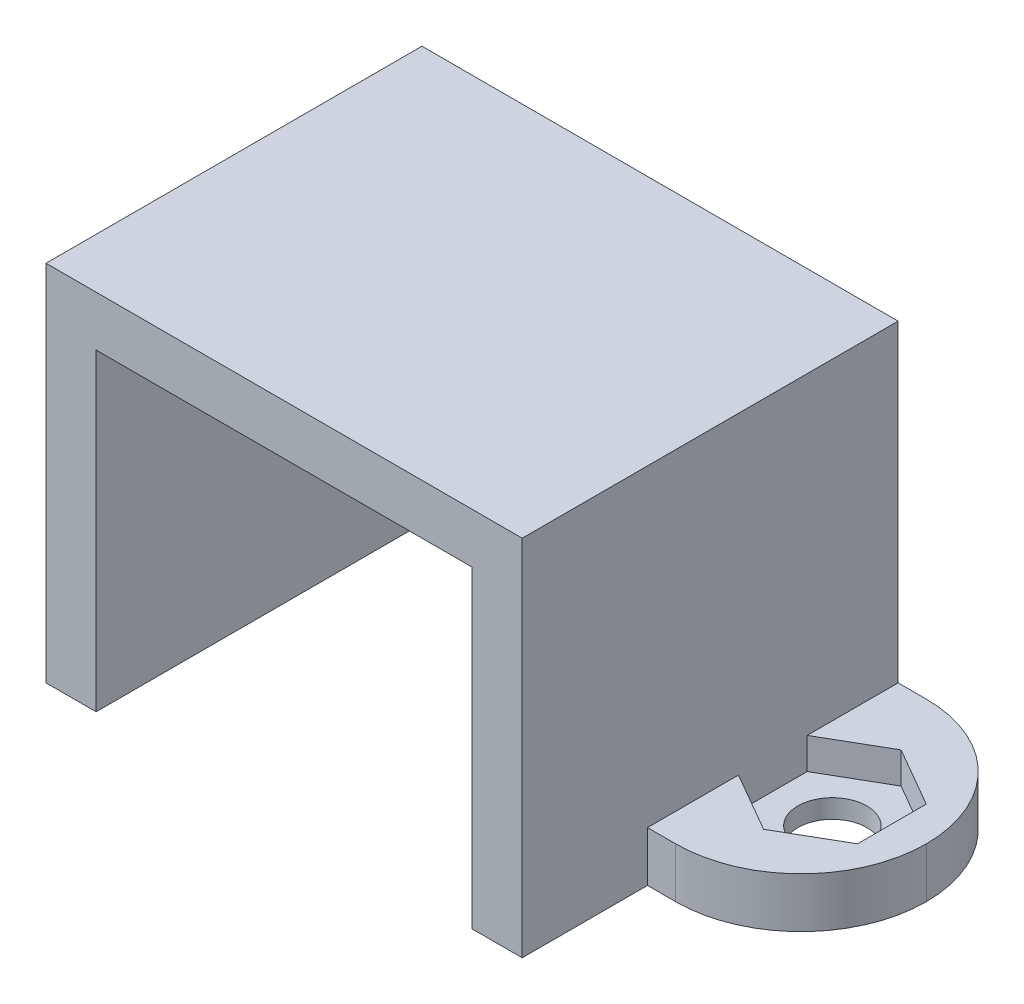
SolidWorks part; units mm, degrees
ref_plane "Front" through (0, 0, 0) normal (0, 0, 1) x (1, 0, 0)
ref_plane "Top" through (0, 0, 0) normal (0, 1, 0) x (1, 0, 0)
ref_plane "Right" through (0, 0, 0) normal (1, 0, 0) x (0, 0, -1)
sketch "草圖1" plane through (0, 0, 0) normal (0, 0, 1) x (1, 0, 0)
  line L0 (-12.5, -10) -> (-6, -10)
  line L1 (-6, -10) -> (-6, 0)
  line L2 (-6, 0) -> (6, 0)
  line L3 (6, 0) -> (6, -10)
  line L4 (6, -10) -> (12.5, -10)
  dimension "D1" = 12
  dimension "D2" = 10
  dimension "D3" = 6.5
  dimension "D4" = 6.5
  dimension "D5" = 10
extrude "伸長-薄件1" add sketch "草圖1" along normal blind 12 thin thin type one direction reverse wall 1.6
sketch "草圖2" plane through (0, -8.4, 0) normal (0, 1, 0) x (1, 0, 0)
  line L0 (-9.5, -4) -> (9.5, -4) construction
  line L2 (-7.6, 0) -> (7.6, 0) construction
  line L4 (0, 0) -> (0, -4) construction
  circle A0 centre (9.5, -4) radius 1.1
  circle A1 centre (-9.5, -4) radius 1.1
  dimension "D2" = 2.2
  dimension "D3" = 4
  dimension "D4" = 19
extrude "除料-伸長1" cut sketch "草圖2" against normal blind 10
sketch "草圖3" plane through (0, -10, 0) normal (0, -1, 0) x (1, 0, 0)
  line L1 (-12.5, 12) -> (-7.6, 12)
  line L2 (-12.5, 12) -> (-12.5, 8)
  line L3 (-12.5, 8) -> (-7.6, 8)
  line L4 (-7.6, 12) -> (-7.6, 8)
  line L6 (12.5, 12) -> (7.6, 12)
  line L7 (12.5, 12) -> (12.5, 8)
  line L8 (12.5, 8) -> (7.6, 8)
  line L9 (7.6, 12) -> (7.6, 8)
  line L10 (-7.6, 12) -> (-7.6, 0) construction
  line L11 (7.6, 12) -> (7.6, 0) construction
  dimension "D1" = 4
  dimension "D2" = 4
extrude "除料-伸長2" cut sketch "草圖3" against normal blind 1.6
fillet "圓角1" radius 4 4 edges at (-12.5, -9.2, 0) (-12.5, -9.2, 8) (12.5, -9.2, 0) (12.5, -9.2, 8)
sketch "草圖4" plane through (0, -8.4, 0) normal (0, 1, 0) x (1, 0, 0)
  line L0 (-7.6, -12) -> (-7.6, 0) construction
  line L1 (-7.6, -5.097) -> (-7.6, -2.903)
  line L2 (-7.6, -2.903) -> (-9.5, -1.8061)
  line L3 (-9.5, -1.8061) -> (-11.4, -2.903)
  line L4 (-11.4, -2.903) -> (-11.4, -5.097)
  line L5 (-11.4, -5.097) -> (-9.5, -6.1939)
  line L6 (-9.5, -6.1939) -> (-7.6, -5.097)
  line L7 (7.6, -5.097) -> (9.5, -6.1939)
  line L8 (9.5, -6.1939) -> (11.4, -5.097)
  line L9 (11.4, -5.097) -> (11.4, -2.903)
  line L10 (11.4, -2.903) -> (9.5, -1.8061)
  line L11 (9.5, -1.8061) -> (7.6, -2.903)
  line L12 (7.6, -2.903) -> (7.6, -5.097)
  line L13 (7.6, -8) -> (7.6, 0) construction
  circle A0 centre (-9.5, -4) radius 1.9 construction
  circle A1 centre (9.5, -4) radius 1.9 construction
extrude "除料-伸長3" cut sketch "草圖4" against normal blind 1
equation "\"1。5\"=10"
